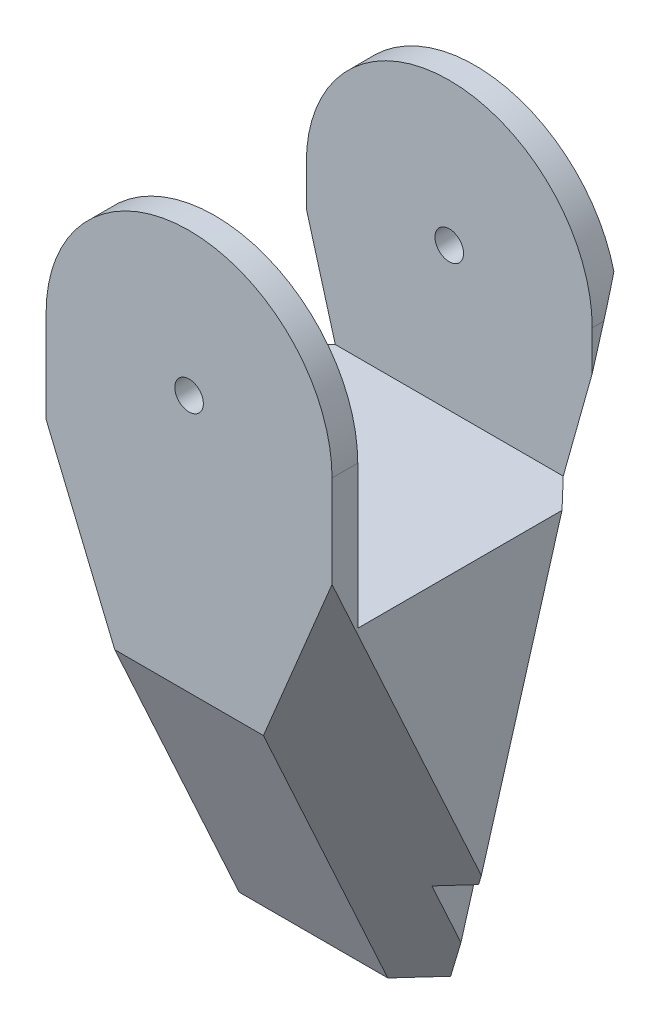
SolidWorks part; units mm, degrees
ref_plane "Front Plane" through (0, 0, 0) normal (0, 0, 1) x (1, 0, 0)
ref_plane "Top Plane" through (0, 0, 0) normal (0, 1, 0) x (1, 0, 0)
ref_plane "Right Plane" through (0, 0, 0) normal (1, 0, 0) x (0, 0, -1)
sketch "Sketch1" plane through (0, 0, 0) normal (0, 1, 0) x (1, 0, 0)
  line L1 (-25, -25) -> (25, -25)
  line L2 (-25, -25) -> (-25, 25)
  line L3 (-25, 25) -> (25, 25)
  line L4 (25, -25) -> (25, 25)
  line L5 (-25, -25) -> (25, 25) construction
  line L6 (-25, 25) -> (25, -25) construction
  point P0 (0, 0)
  dimension "D1" = 50
  dimension "D2" = 50
extrude "Boss-Extrude1" add sketch "Sketch1" along normal blind 100
sketch "Sketch4" plane through (0, 0, -25) normal (0, 0, -1) x (-1, 0, 0)
  line L0 (25, 100) -> (25, 0) construction
  line L1 (-25, 100) -> (25, 100)
  line L2 (-25, 100) -> (-25, 125)
  line L4 (25, 100) -> (25, 125)
  arc A0 (-25, 125) -> (25, 125) centre (0, 125) cw
  circle A1 centre (0, 125) radius 2.5
  dimension "D2" = 5
  dimension "D1" = 25
extrude "Boss-Extrude2" add sketch "Sketch4" against normal blind 4.5
mirror "Mirror2" about plane through (0, 0, 0) normal (0, 0, 1) of "Boss-Extrude2"
sketch "Sketch5" plane through (25, 0, 0) normal (-1, 0, 0) x (0, 0, 1)
  line L0 (0, -27.5) -> (0, 27.5) construction
  line L1 (27.5, 0) -> (-27.5, 0) construction
  line L2 (-25, 125) -> (-25, 0) construction
  line L3 (25, 25) -> (25, 0)
  line L4 (25, 0) -> (-25, 0)
  line L5 (-25, 0) -> (-25, 25)
  arc A0 (-25, 25) -> (25, 25) centre (0, 25) ccw
  circle A1 centre (0, 25) radius 2.5
  point P15 (0, 0)
  line M6 (25, 0) -> (-25, 0)
  line M7 (-25, 0) -> (-25, 125)
  line M13 (25, 125) -> (25, 0)
  dimension "D1" = 5
extrude "Cut-Extrude1" cut sketch "Sketch5" along normal through all both and the other way through all contours A0 L4 M7 | A0 M6 M13 | A1 region at (25, 5.5842, -19.4158) region at (25, 5.5842, 19.4158)
sketch "Sketch6" plane through (25, 0, 0) normal (1, 0, 0) x (0, 0, -1)
  line L0 (-25, 50) -> (25, 50)
  line L1 (-25, 125) -> (-25, 25) construction
  line L2 (25, 125) -> (25, 25) construction
  line L3 (25, 50) -> (25, 0)
  line L4 (27.5, 0) -> (-27.5, 0) construction
  line L5 (25, 0) -> (-25, 0)
  line L6 (-25, 0) -> (-25, 50)
  circle A0 centre (0, 25) radius 25 construction
extrude "Cut-Extrude2" cut sketch "Sketch6" against normal blind 4.5
mirror "Mirror3" about plane through (0, 0, 0) normal (1, 0, 0) of "Cut-Extrude2"
sketch "Sketch8" plane through (25, 0, 0) normal (1, 0, 0) x (0, 0, -1)
  line L0 (-25, 80) -> (-3.2509, 32.4045)
  line L1 (-25, 125) -> (-25, 50) construction
  line L3 (-3.2509, 32.4045) -> (11.0865, 32.4045)
  line L5 (11.0865, 32.4045) -> (25, 80)
  line L6 (25, 125) -> (25, 50) construction
  line L7 (-20.5, 100) -> (20.5, 100) construction
  line L8 (-25, 80) -> (-42.0954, 0)
  line L9 (-42.0954, 0) -> (18.7554, -23.2781)
  line L10 (18.7554, -23.2781) -> (47.597, 33.9049)
  line L11 (47.597, 33.9049) -> (25, 80)
  dimension "D1" = 20
  dimension "D2" = 20
extrude "Cut-Extrude5" cut sketch "Sketch8" against normal through all both and the other way through all
chamfer "Chamfer1" distance 12 angle 45 2 edges at (25, 65, 18.1457) (-25, 65, 18.1457)
chamfer "Chamfer2" distance 15 angle 45 2 edges at (25, 65, -20.6151) (-25, 65, -20.6151)
